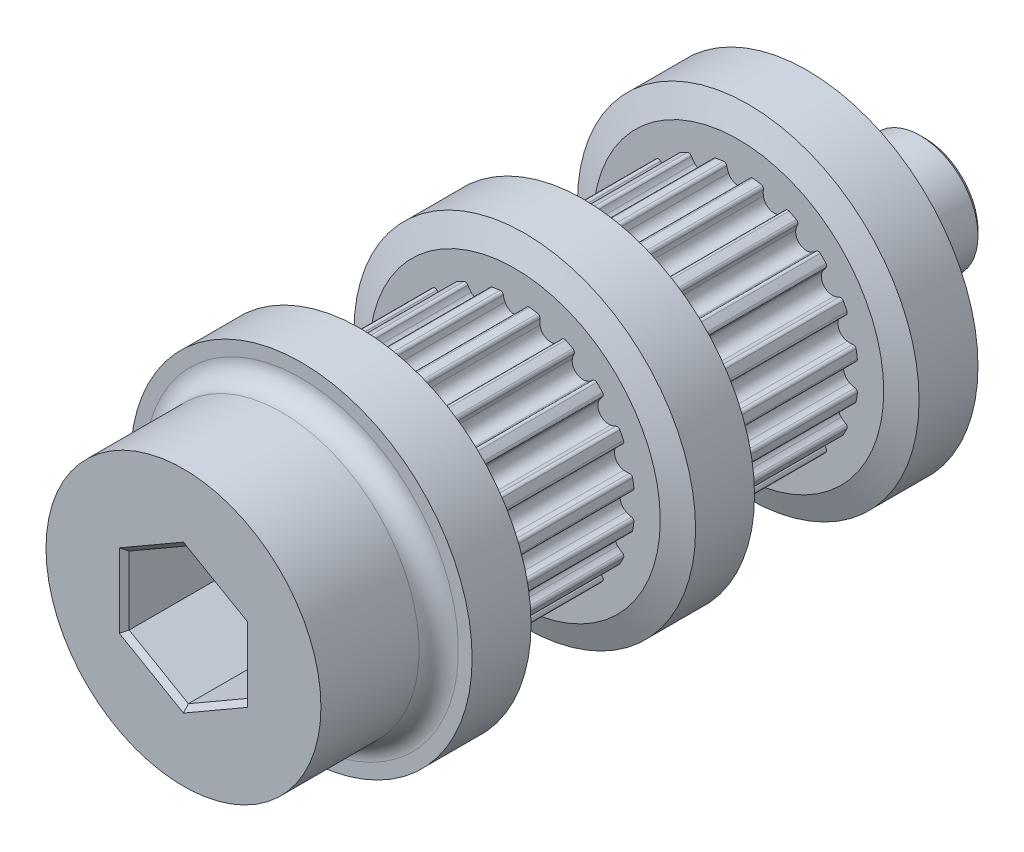
SolidWorks part; units mm, degrees
ref_plane "Front Plane" through (0, 0, 0) normal (0, 0, 1) x (1, 0, 0)
ref_plane "Top Plane" through (0, 0, 0) normal (0, 1, 0) x (1, 0, 0)
ref_plane "Right Plane" through (0, 0, 0) normal (1, 0, 0) x (0, 0, -1)
sketch "Sketch1" plane through (0, 0, 0) normal (0, 0, 1) x (1, 0, 0)
  point P0 (-2.841, 8.6995)
  line B0 (-1.7499, 5.3585) -> (1.7499, 5.3585) construction
  line B1 (0, 0) -> (0, 5.3585) construction
  line B2 (0, 5.3585) -> (0, 11.2111) construction
  line B3 (0, 6.3625) -> (1.9751, 6.0482) construction
  line B4 (1.9751, 6.0482) -> (2.6648, 5.8229) construction
  line B5 (1.9751, 6.0482) -> (1.7499, 5.3585) construction
  line B6 (-1.9751, 6.0482) -> (-1.7499, 5.3585) construction
  line B7 (-1.8963, 5.8067) -> (-2.841, 8.6995)
  line B8 (-2.841, 8.6995) -> (2.841, 8.6995)
  line B9 (2.841, 8.6995) -> (1.8963, 5.8067)
  circle B10 centre (0, 0) radius 6.3625 construction
  circle B11 centre (0, 0) radius 8.6995 construction
  circle B12 centre (0, 0) radius 6.1085 construction
  arc B13 (-0.4989, 5.6703) -> (0.4989, 5.6703) centre (0, 5.9135) ccw
  arc B14 (-0.4989, 5.6703) -> (-0.5855, 5.9387) centre (0.4, 6.1085) cw
  arc B15 (-1.8963, 5.8067) -> (-0.7518, 6.0621) centre (0, 0) cw
  arc B16 (-0.5855, 5.9387) -> (-0.7518, 6.0621) centre (-0.7333, 5.9132) ccw
  arc B17 (1.8963, 5.8067) -> (0.7518, 6.0621) centre (0, 0) ccw
  arc B18 (0.5855, 5.9387) -> (0.7518, 6.0621) centre (0.7333, 5.9132) cw
  arc B19 (0.4989, 5.6703) -> (0.5855, 5.9387) centre (-0.4, 6.1085) ccw
sketch_block_instance "Block-Gt Timing Belt Pulley Groove-1"
sketch_block "Block-Gt Timing Belt Pulley Groove" parameters "D1"=12.725, "D2"=17.399, "D6"=0.555, "D7"=1, "D9"=0.15, "D3"=9.6972, "D4"=4.8486, "D5"=2, "D8"=0.254, "D10"=0.4, "D11"=0.75
sketch "Sketch9" plane through (0, 0, 0) normal (0, 0, 1) x (1, 0, 0)
  line L1 (0, 3.1927) -> (-2.765, 1.5964) construction
  line L2 (-2.765, 1.5964) -> (-2.765, -1.5964) construction
  line L3 (-2.765, -1.5964) -> (0, -3.1927) construction
  line L4 (0, -3.1927) -> (2.765, -1.5964) construction
  line L5 (2.765, -1.5964) -> (2.765, 1.5964) construction
  line L6 (2.765, 1.5964) -> (0, 3.1927) construction
  circle A0 centre (0, 0) radius 2.765 construction
  dimension "D1" = 5.53
sketch "Sketch2" plane through (0, 0, 0) normal (1, 0, 0) x (0, 0, -1)
  line L0 (-3.685, 6.1085) -> (3.685, 6.1085)
  line L1 (-18.57, 0) -> (7.19, 0) construction
  line L2 (-3.685, 6.1085) -> (-3.685, 7.404)
  line L3 (-3.685, 7.404) -> (-4.19, 8.6995)
  line L4 (-4.19, 8.6995) -> (-7.19, 8.6995)
  line L5 (-7.19, 8.6995) -> (-7.695, 7.404)
  line L6 (3.685, 6.1085) -> (3.685, 7.404)
  line L7 (3.685, 7.404) -> (4.19, 8.6995)
  line L8 (4.19, 8.6995) -> (7.19, 8.6995)
  line L9 (7.19, 8.6995) -> (7.19, 0)
  line L10 (0, 6.1085) -> (0, 0) construction
  line L11 (-18.57, 0) -> (7.19, 0)
  line L12 (-7.695, 7.404) -> (-7.695, 6.1085)
  line L13 (-7.695, 6.1085) -> (-15.065, 6.1085)
  line L14 (-15.065, 6.1085) -> (-15.065, 7.404)
  line L15 (-15.065, 7.404) -> (-15.57, 8.6995)
  line L16 (-15.57, 8.6995) -> (-18.57, 8.6995)
  line L17 (-18.57, 8.6995) -> (-18.57, 0)
  point P19 (-16.5212, 0)
  dimension "D1" = 12.217
  dimension "D2" = 7.37
  dimension "D3" = 8.38
  dimension "D4" = 17.399
  dimension "D5" = 14.808
  dimension "D6" = 3
revolve "Revolve1" add sketch "Sketch2" angle 360 about L11
sketch "Sketch10" plane through (0, 0, 18.57) normal (0, 0, 1) x (1, 0, 0)
  circle A0 centre (0, 0) radius 7
  dimension "D1" = 14
extrude "Boss-Extrude1" add sketch "Sketch10" along normal blind 6
sketch "Sketch13" plane through (0, 0, -7.19) normal (0, 0, -1) x (-1, 0, 0)
  circle A0 centre (0, 0) radius 2.95
  dimension "D1" = 5.9
extrude "Boss-Extrude2" add sketch "Sketch13" along normal blind 6
sketch "Sketch5" plane through (0, 0, 0) normal (0, 0, 1) x (1, 0, 0)
  line L0 (2.841, 8.6995) -> (1.8963, 5.8067) construction
  line L1 (-1.8963, 5.8067) -> (-2.841, 8.6995) construction
  line L2 (-2.841, 8.6995) -> (2.841, 8.6995) construction
  line L3 (2.841, 8.6995) -> (1.8963, 5.8067)
  line L4 (-1.8963, 5.8067) -> (-2.841, 8.6995)
  line L5 (-2.841, 8.6995) -> (2.841, 8.6995)
  arc A0 (1.8963, 5.8067) -> (0.7518, 6.0621) centre (0, 0) ccw construction
  arc A1 (0.7518, 6.0621) -> (0.5855, 5.9387) centre (0.7333, 5.9132) ccw construction
  arc A2 (0.4989, 5.6703) -> (0.5855, 5.9387) centre (-0.4, 6.1085) ccw construction
  arc A3 (-0.4989, 5.6703) -> (0.4989, 5.6703) centre (0, 5.9135) ccw construction
  arc A4 (-0.5855, 5.9387) -> (-0.4989, 5.6703) centre (0.4, 6.1085) ccw construction
  arc A5 (-0.5855, 5.9387) -> (-0.7518, 6.0621) centre (-0.7333, 5.9132) ccw construction
  arc A6 (-0.7518, 6.0621) -> (-1.8963, 5.8067) centre (0, 0) ccw construction
  arc A7 (1.8963, 5.8067) -> (0.7518, 6.0621) centre (0, 0) ccw
  arc A8 (0.7518, 6.0621) -> (0.5855, 5.9387) centre (0.7333, 5.9132) ccw
  arc A9 (0.4989, 5.6703) -> (0.5855, 5.9387) centre (-0.4, 6.1085) ccw
  arc A10 (-0.4989, 5.6703) -> (0.4989, 5.6703) centre (0, 5.9135) ccw
  arc A11 (-0.5855, 5.9387) -> (-0.4989, 5.6703) centre (0.4, 6.1085) ccw
  arc A12 (-0.5855, 5.9387) -> (-0.7518, 6.0621) centre (-0.7333, 5.9132) ccw
  arc A13 (-0.7518, 6.0621) -> (-1.8963, 5.8067) centre (0, 0) ccw
extrude "Cut-Extrude1" cut sketch "Sketch5" against normal up to surface and the other way up to surface up to face at (6.1085, 0, -3.685) other way up to face at (7.404, 0, 3.685)
sketch "Sketch7" plane through (0, 0, 7.695) normal (0, 0, 1) x (1, 0, 0)
  line L3 (1.8963, 5.8067) -> (2.841, 8.6995)
  line L4 (2.841, 8.6995) -> (-2.841, 8.6995)
  line L5 (-2.841, 8.6995) -> (-1.8963, 5.8067)
  line L6 (1.8963, 5.8067) -> (2.841, 8.6995)
  line L7 (2.841, 8.6995) -> (-2.841, 8.6995)
  line L8 (-2.841, 8.6995) -> (-1.8963, 5.8067)
  arc A7 (-0.7518, 6.0621) -> (-1.8963, 5.8067) centre (0, 0) ccw
  arc A8 (-0.5855, 5.9387) -> (-0.7518, 6.0621) centre (-0.7333, 5.9132) ccw
  arc A9 (-0.5855, 5.9387) -> (-0.4989, 5.6703) centre (0.4, 6.1085) ccw
  arc A10 (-0.4989, 5.6703) -> (0.4989, 5.6703) centre (0, 5.9135) ccw
  arc A11 (0.4989, 5.6703) -> (0.5855, 5.9387) centre (-0.4, 6.1085) ccw
  arc A12 (0.7518, 6.0621) -> (0.5855, 5.9387) centre (0.7333, 5.9132) ccw
  arc A13 (1.8963, 5.8067) -> (0.7518, 6.0621) centre (0, 0) ccw
  arc A14 (-0.7518, 6.0621) -> (-1.8963, 5.8067) centre (0, 0) ccw
  arc A15 (-0.5855, 5.9387) -> (-0.7518, 6.0621) centre (-0.7333, 5.9132) ccw
  arc A16 (-0.5855, 5.9387) -> (-0.4989, 5.6703) centre (0.4, 6.1085) ccw
  arc A17 (-0.4989, 5.6703) -> (0.4989, 5.6703) centre (0, 5.9135) ccw
  arc A18 (0.4989, 5.6703) -> (0.5855, 5.9387) centre (-0.4, 6.1085) ccw
  arc A19 (0.7518, 6.0621) -> (0.5855, 5.9387) centre (0.7333, 5.9132) ccw
  arc A20 (1.8963, 5.8067) -> (0.7518, 6.0621) centre (0, 0) ccw
  dimension "D1" = 0
extrude "Cut-Extrude3" cut sketch "Sketch7" along normal up to surface (7.37 mm away) up to face at (7.404, 0, 15.065)
pattern_circular "CirPattern1" count 20 over 360 about axis through (0, 0, 18.57) along (0, 0, 1) of "Cut-Extrude1", "Cut-Extrude3"
sketch "Sketch11" plane through (0, 0, 18.57) normal (0, 0, 1) x (1, 0, 0)
  line L24 (0, 3.4814) -> (-3.015, 1.7407)
  line L25 (-3.015, 1.7407) -> (-3.015, -1.7407)
  line L26 (-3.015, -1.7407) -> (0, -3.4814)
  line L27 (0, -3.4814) -> (3.015, -1.7407)
  line L28 (3.015, -1.7407) -> (3.015, 1.7407)
  line L29 (3.015, 1.7407) -> (0, 3.4814)
  line L30 (0, 3.4814) -> (-3.015, 1.7407)
  line L31 (-3.015, 1.7407) -> (-3.015, -1.7407)
  line L32 (-3.015, -1.7407) -> (0, -3.4814)
  line L33 (0, -3.4814) -> (3.015, -1.7407)
  line L34 (3.015, -1.7407) -> (3.015, 1.7407)
  line L35 (3.015, 1.7407) -> (0, 3.4814)
  dimension "D1" = 0.25
extrude "Cut-Extrude4" cut sketch "Sketch11" along normal through all
fillet "Fillet1" radius 1 2 edges at (7, 0, 18.57) (-2.95, 0, -7.19)
chamfer "Chamfer1" distance 0.25 angle 45 7 edges at (-2.95, 0, -13.19) (-3.015, 0, 24.57) (-1.5075, 2.6111, 24.57) (1.5075, 2.6111, 24.57) (3.015, 0, 24.57) (1.5075, -2.6111, 24.57) (-1.5075, -2.6111, 24.57)
